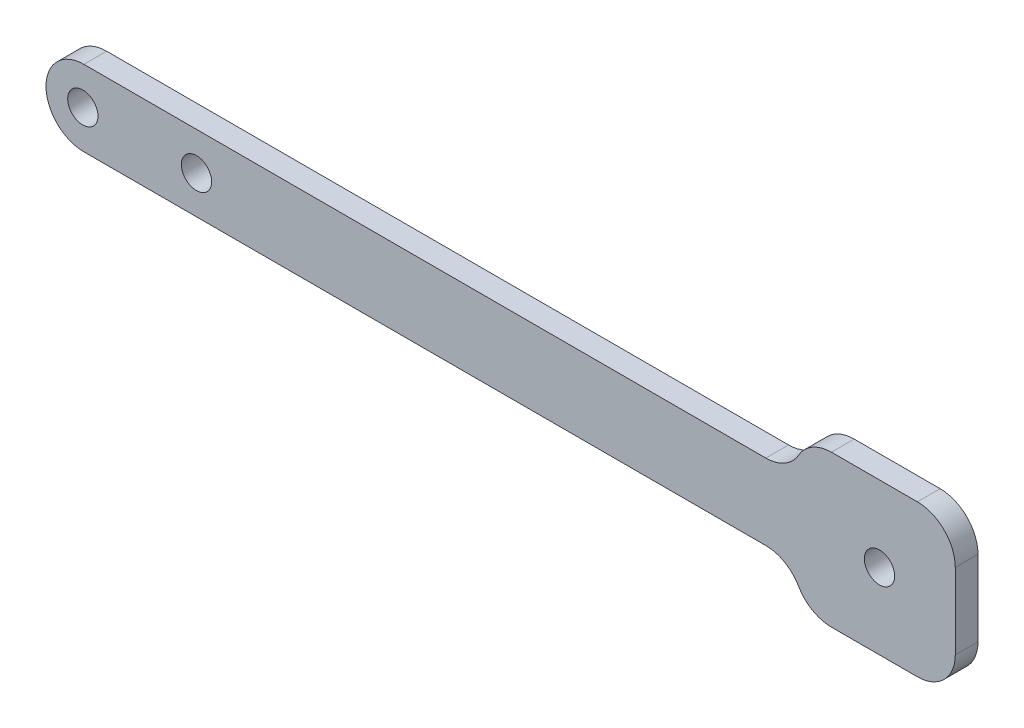
SolidWorks part; units mm, degrees
ref_plane "前视基准面" through (0, 0, 0) normal (0, 0, 1) x (1, 0, 0)
ref_plane "上视基准面" through (0, 0, 0) normal (0, 1, 0) x (1, 0, 0)
ref_plane "右视基准面" through (0, 0, 0) normal (1, 0, 0) x (0, 0, -1)
other "Configuration Table"
sketch "草图1" plane through (0, 0, 0) normal (0, 0, 1) x (1, 0, 0)
  line L0 (40, 0) -> (-60, 0) construction
  line L1 (-60, 10) -> (60, 10) construction
  line L2 (-60, 10) -> (-60, -10) construction
  line L3 (-60, -10) -> (60, -10) construction
  line L4 (60, 10) -> (60, -10) construction
  line L5 (-60, 10) -> (60, -10) construction
  line L6 (-60, -10) -> (60, 10) construction
  line L7 (60, 10) -> (40, 10) construction
  line L8 (60, 10) -> (60, -10) construction
  line L9 (60, -10) -> (40, -10) construction
  line L10 (40, 10) -> (40, -10) construction
  line L11 (60, 10) -> (40, -10) construction
  line L12 (60, -10) -> (40, 10) construction
  line L13 (-60, 5) -> (40, 5)
  line L14 (-60, 5) -> (40, 5) construction
  line L15 (-60, 5) -> (-60, -5) construction
  line L16 (-60, -5) -> (40, -5) construction
  line L17 (40, 5) -> (40, -5) construction
  line L18 (-60, 5) -> (40, -5) construction
  line L19 (-60, -5) -> (40, 5) construction
  line L20 (40, 5) -> (40, 10)
  line L21 (40, 10) -> (60, 10)
  line L22 (60, 10) -> (60, -10)
  line L23 (60, -10) -> (40, -10)
  line L24 (40, -10) -> (40, -5)
  line L25 (40, -5) -> (-60, -5)
  line L26 (-60, -5) -> (-60, 5)
  line L28 (-55.1385, 0) -> (-40.1385, 0) construction
  circle A0 centre (-55.1385, 0) radius 2
  circle A1 centre (-40.1385, 0) radius 2
  circle A2 centre (50, 0) radius 2
  point P0 (0, 0)
  point P8 (50, 0)
  point P11 (-10, 0)
  dimension "D1" = 20
  dimension "D2" = 120
  dimension "D3" = 20
  dimension "D4" = 10
extrude "凸台-拉伸1" add sketch "草图1" along normal blind 3
fillet "圆角2" radius 5 4 edges at (-60, -5, 1.5) (-60, 5, 1.5) (60, -10, 1.5) (60, 10, 1.5)
fillet "圆角3" radius 5 2 edges at (40, -5, 1.5) (40, 5, 1.5)
fillet "圆角4" radius 5 2 edges at (40, 10, 1.5) (40, -10, 1.5)
